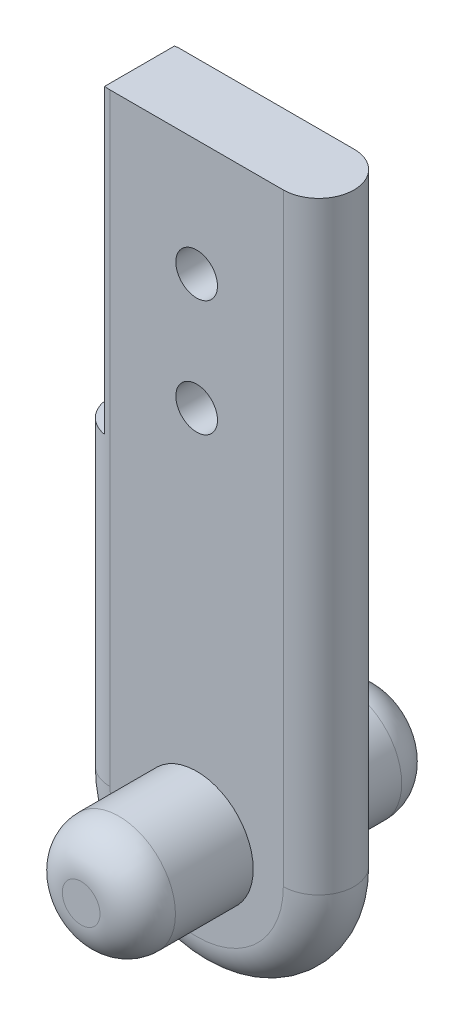
SolidWorks part; units mm, degrees
ref_plane "Front Plane" through (0, 0, 0) normal (0, 0, 1) x (1, 0, 0)
ref_plane "Top Plane" through (0, 0, 0) normal (0, 1, 0) x (1, 0, 0)
ref_plane "Right Plane" through (0, 0, 0) normal (1, 0, 0) x (0, 0, -1)
sketch "Sketch1" plane through (0, 0, 0) normal (0, 0, 1) x (1, 0, 0)
  line L0 (34.5724, 0) -> (34.5724, 50.8)
  line L1 (34.5724, 50.8) -> (55.1214, 50.8)
  line L2 (55.1214, 50.8) -> (55.1214, 0)
  arc A0 (34.5724, 0) -> (55.1214, 0) centre (44.8469, 0) ccw
  circle A1 centre (44.8469, 0) radius 4.5641
  dimension "D1" = 9.1281
  dimension "D2" = 10.2745
  dimension "D3" = 50.8
extrude "Boss-Extrude1" add sketch "Sketch1" along normal mid plane 5.9531
sketch "Sketch2" plane through (0, 0, 0) normal (0, 0, 1) x (1, 0, 0)
  circle A0 centre (44.8469, 0) radius 4.7625
extrude "Boss-Extrude2" add sketch "Sketch2" along normal mid plane 25.4
fillet "Fillet1" radius 3.175 2 edges at (49.6094, 0, -12.7) (49.6094, 0, 12.7)
fillet "Fillet2" 6 edges at (44.8469, -10.2745, 2.9766) (55.1214, 25.4, 2.9766) (34.5724, 25.4, 2.9766) (44.8469, -10.2745, -2.9766) (34.5724, 25.4, -2.9766) (55.1214, 25.4, -2.9766) type full round first side face at (44.8469, 22.8314, 2.9766) second side face at (44.8469, 22.8314, -2.9766) middle face at (34.5724, 25.4, 0) middle face at (44.8469, -5.1373, 0) middle face at (55.1214, 25.4, 0)
sketch "Sketch3" plane through (0, 50.8, 0) normal (0, 1, 0) x (1, 0, 0)
  line L0 (44.8469, 2.9766) -> (44.8469, -2.9766) construction
  line L1 (52.1448, 2.9766) -> (37.5489, 2.9766) construction
  line L2 (52.1448, -2.9766) -> (37.5489, -2.9766) construction
  line L3 (37.0681, -2.9766) -> (37.0681, 2.9766)
  line L4 (37.0681, 2.9766) -> (34.5724, 2.9766)
  line L5 (34.5724, 2.9766) -> (34.5724, -2.9766)
  line L6 (34.5724, -2.9766) -> (37.0681, -2.9766)
  arc A0 (37.5489, 2.9766) -> (37.5489, -2.9766) centre (37.5489, 0) ccw construction
  dimension "D1" = 7.7788
extrude "Cut-Extrude1" cut sketch "Sketch3" against normal blind 25.4
sketch "Sketch4" plane through (0, 0, -2.9766) normal (0, 0, -1) x (-1, 0, 0)
  line L0 (-44.8469, -961.9) -> (-44.8469, 49038.1) construction
  line L1 (-52.1448, 50.8) -> (-37.5489, 50.8) construction
  point P1 (-44.8469, 41.021)
  point P5 (-44.8469, 50.8)
  point P6 (-44.8469, 31.242)
  dimension "D1" = 19.558
  dimension "D2" = 9.779
hole_wizard "#6-32 Tapped Hole1" positions "Sketch6" profile "Sketch5" tap size "#6-32" standard "ANSI Inch" end condition through all
sketch "Sketch6" plane through (0, 0, -2.9766) normal (0, 0, -1) x (-1, 0, 0)
  point P0 (-44.8469, 41.021)
  point P3 (-44.8469, 31.242)
sketch "Sketch5" plane through (44.8469, 41.021, -2.9766) normal (1, 0, 0) x (0, 1, 0)
  line L0 (0, 0) -> (0, 15.6766)
  line L1 (0, 15.6766) -> (1.7526, 15.6766)
  line L2 (1.7526, 15.6766) -> (1.7526, 0)
  line L5 (1.7526, 0) -> (0, 0)
  line L11 (0, -6.35) -> (0, 107.95) construction
  dimension "Thread Major Dia." = 3.5052
  dimension "Thru Tap Drill Depth" = 15.6766
equation "\"D2@Sketch4\"=\"D1@Sketch4\"/2"
